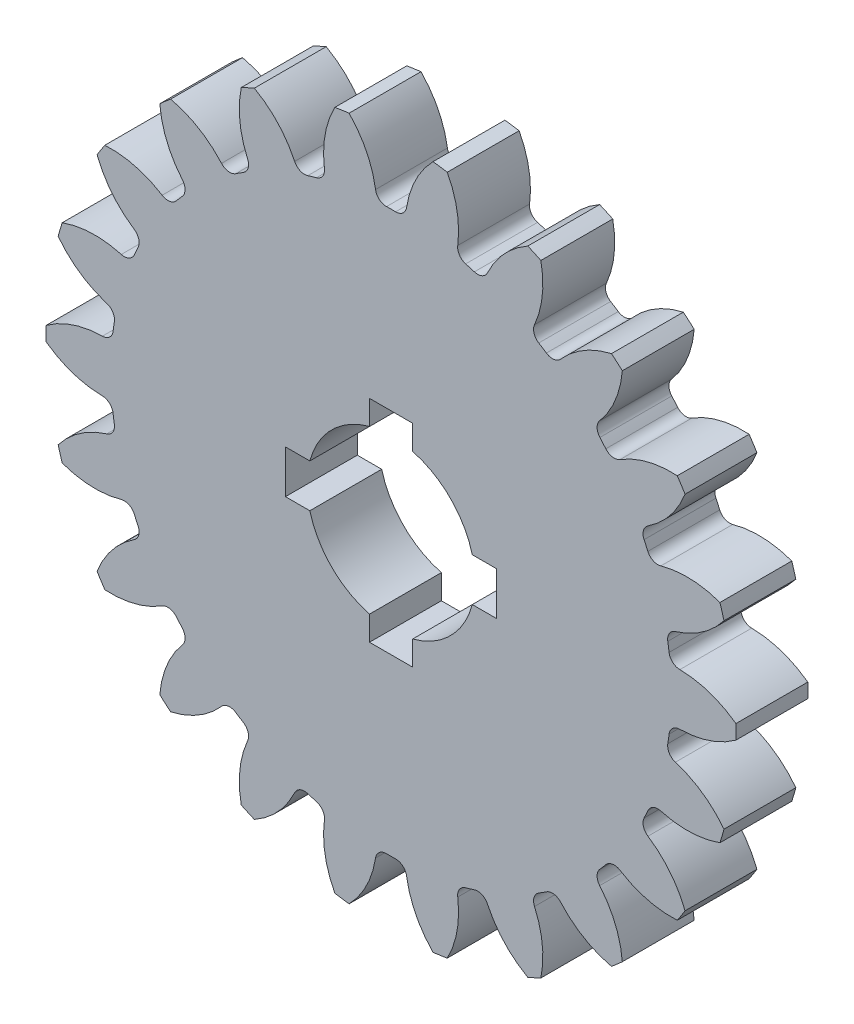
SolidWorks part; units mm, degrees
ref_plane "Front Plane" through (0, 0, 0) normal (0, 0, 1) x (1, 0, 0)
ref_plane "Top Plane" through (0, 0, 0) normal (0, 1, 0) x (1, 0, 0)
ref_plane "Right Plane" through (0, 0, 0) normal (1, 0, 0) x (0, 0, -1)
sketch "Sketch1" plane through (0, 0, 0) normal (0, 0, 1) x (1, 0, 0)
  line L4 (-1.0109, 19.4738) -> (0, 0) construction
  line L5 (0, 0) -> (0, 24) construction
  line L6 (0, 0) -> (3.4156, 23.7557) construction
  line L7 (-1.6208, 21.9402) -> (0.7584, 23.0107) construction
  line L8 (-1.6208, 21.9402) -> (0.3989, 22.0894) construction
  line L11 (1.6208, 21.9402) -> (-1.6208, 21.9402) construction
  circle A0 centre (0, 0) radius 19.5
  circle A1 centre (0, 0) radius 22 construction
  circle A2 centre (0, 0) radius 24
  arc A3 (-2.9199, 23.8217) -> (-1.0109, 19.4738) centre (-7.7084, 19.1261) cw
  arc A4 (2.9199, 23.8217) -> (1.0109, 19.4738) centre (7.7084, 19.1261) ccw
  point P5 (-22, 0)
  point P6 (-24, 0)
  point P7 (-19.5, 0)
  point P12 (-1.6208, 21.9402)
  point P22 (1.6208, 21.9402)
  dimension "D5" = 44
  dimension "D1" = 2.5
  dimension "D2" = 2
  dimension "D3" = 20
  dimension "D4" = 3.2416
  dimension "D6" = 8.182
  dimension "D7" = 0.5
extrude "Boss-Extrude1" add sketch "Sketch1" against normal blind 5 contours A2
extrude "Cut-Extrude1" cut sketch "Sketch1<4>" against normal blind 10 contours A4 A2 A3 A0 region at (0, 22.1455, 0)
sketch "Sketch1<4>" plane through (0, 0, 0) normal (0, 0, 1) x (1, 0, 0) same geometry as "Sketch1"
fillet "Fillet2" radius 0.76 2 edges at (1.0109, 19.4738, -2.5) (-1.0109, 19.4738, -2.5)
ref_axis "Axis1" through (0, 0, 0) along (0, 0, 1)
pattern_circular "CirPattern2" count 22 over 360 about axis through (0, 0, 0) along (0, 0, 1) of "Cut-Extrude1", "Fillet2"
sketch "Sketch2" plane through (0, 0, 0) normal (0, 0, 1) x (1, 0, 0)
  line L0 (-1.5, 5.6528) -> (-1.5, 7.3485)
  line L1 (-1.5, 4.3485) -> (1.5, 4.3485) construction
  line L2 (-1.5, 4.3485) -> (-1.5, 7.3485) construction
  line L3 (-1.5, 7.3485) -> (1.5, 7.3485) construction
  line L4 (1.5, 4.3485) -> (1.5, 7.3485) construction
  line L5 (-1.5, 4.3485) -> (1.5, 7.3485) construction
  line L6 (-1.5, 7.3485) -> (1.5, 4.3485) construction
  line L7 (4.3485, -1.5) -> (7.3485, -1.5) construction
  line L8 (4.3485, -1.5) -> (4.3485, 1.5) construction
  line L9 (4.3485, 1.5) -> (7.3485, 1.5) construction
  line L10 (7.3485, -1.5) -> (7.3485, 1.5) construction
  line L11 (4.3485, -1.5) -> (7.3485, 1.5) construction
  line L12 (4.3485, 1.5) -> (7.3485, -1.5) construction
  line L13 (-1.5, -7.3485) -> (1.5, -7.3485) construction
  line L14 (-1.5, -7.3485) -> (-1.5, -4.3485) construction
  line L15 (-1.5, -4.3485) -> (1.5, -4.3485) construction
  line L16 (1.5, -7.3485) -> (1.5, -4.3485) construction
  line L17 (-1.5, -7.3485) -> (1.5, -4.3485) construction
  line L18 (-1.5, -4.3485) -> (1.5, -7.3485) construction
  line L19 (-7.3485, -1.5) -> (-4.3485, -1.5) construction
  line L20 (-7.3485, -1.5) -> (-7.3485, 1.5) construction
  line L21 (-7.3485, 1.5) -> (-4.3485, 1.5) construction
  line L22 (-4.3485, -1.5) -> (-4.3485, 1.5) construction
  line L23 (-7.3485, -1.5) -> (-4.3485, 1.5) construction
  line L24 (-7.3485, 1.5) -> (-4.3485, -1.5) construction
  line L25 (-1.5, 7.3485) -> (1.5, 7.3485)
  line L26 (1.5, 7.3485) -> (1.5, 5.6528)
  line L27 (5.6528, 1.5) -> (7.3485, 1.5)
  line L28 (7.3485, 1.5) -> (7.3485, -1.5)
  line L29 (7.3485, -1.5) -> (5.6528, -1.5)
  line L30 (1.5, -7.3485) -> (1.5, -5.6528)
  line L31 (1.5, -7.3485) -> (-1.5, -7.3485)
  line L32 (-1.5, -7.3485) -> (-1.5, -5.6528)
  line L33 (-5.6528, -1.5) -> (-7.3485, -1.5)
  line L34 (-7.3485, -1.5) -> (-7.3485, 1.5)
  line L35 (-7.3485, 1.5) -> (-5.6528, 1.5)
  circle A0 centre (0, 0) radius 7.5 construction
  arc A1 (-1.5, 5.6528) -> (-5.6528, 1.5) centre (0, 0) ccw
  arc A2 (5.6528, 1.5) -> (1.5, 5.6528) centre (0, 0) ccw
  arc A3 (1.5, -5.6528) -> (5.6528, -1.5) centre (0, 0) ccw
  arc A4 (-5.6528, -1.5) -> (-1.5, -5.6528) centre (0, 0) ccw
  point P3 (0, 5.8485)
  point P8 (5.8485, 0)
  point P13 (0, -5.8485)
  point P18 (-5.8485, 0)
  dimension "D1" = 15
  dimension "D2" = 3
extrude "Cut-Extrude2" cut sketch "Sketch2" against normal up to surface (5 mm away) up to face at (0, 0, -5)
equation "\"backlash\"= 0.1mm"
equation "\"module\"= 2mm"
equation "\"pressureAngle\"= 20deg"
equation "\"width\"= 10mm"
equation "\"D1@Sketch1\"= 1.25 * \"module\""
equation "\"D2@Sketch1\"=\"module\""
equation "\"D5@Sketch1\"=\"module\"*\"numberOfTeeth\""
equation "\"D1@Boss-Extrude1\"=\"width\"-5"
equation "\"D3@Sketch1\"=\"pressureAngle\""
equation "\"D1@Cut-Extrude1\"=\"width\""
equation "\"D1@CirPattern2\"=\"numberOfTeeth\""
equation "\"D1@Fillet2\"=0.38*\"module\""
equation "\"D4@Sketch1\"=pi*\"module\"/2+\"backlash\""
equation "\"numberOfTeeth\"= 22"
equation "\"D6@Sketch1\"=180/\"numberOfTeeth\""
equation "\"toothTipProfile\"= 1mm"
equation "\"D7@Sketch1\"=\"toothTipProfile\"/2"
equation "\"lengthOverallRack\"= pi * \"module\" * \"numberOfTeethRack\""
equation "\"numberOfTeethRack\"= 20"
